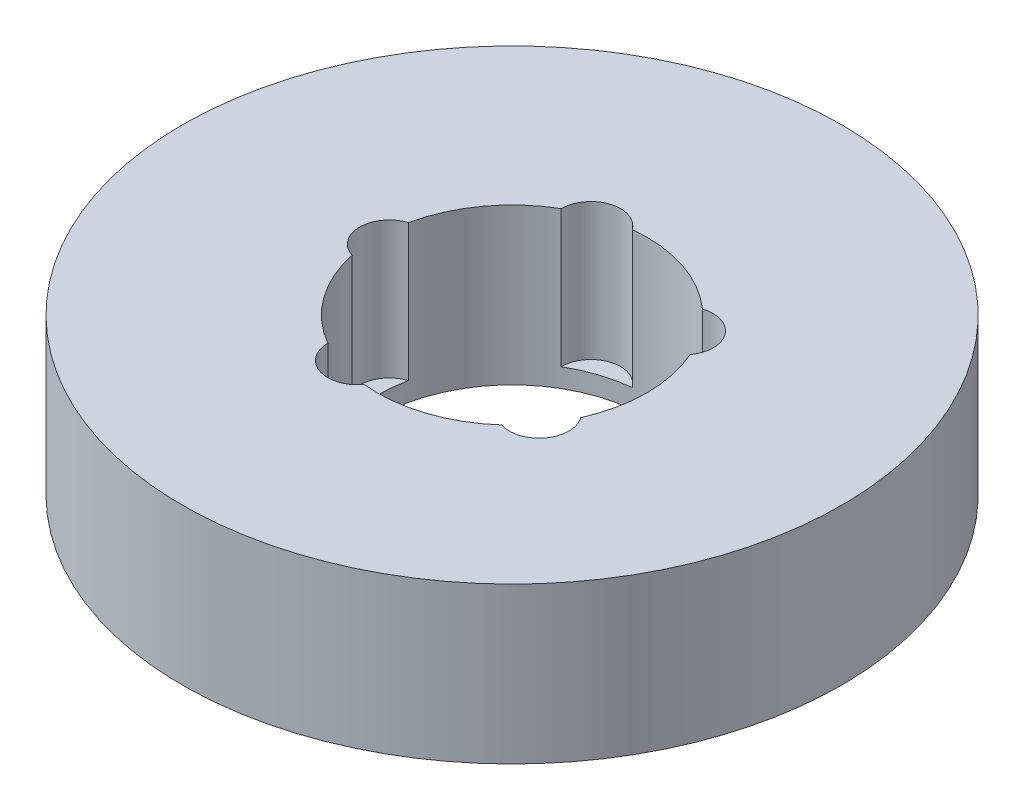
SolidWorks part; units mm, degrees
ref_plane "Front Plane" through (0, 0, 0) normal (0, 0, 1) x (1, 0, 0)
ref_plane "Top Plane" through (0, 0, 0) normal (0, 1, 0) x (1, 0, 0)
ref_plane "Right Plane" through (0, 0, 0) normal (1, 0, 0) x (0, 0, -1)
sketch "Sketch1" plane through (0, 0, 0) normal (0, 1, 0) x (1, 0, 0)
  circle A0 centre (0, 0) radius 55
  dimension "FLANGE_OD" = 110
extrude "Boss-Extrude1" add sketch "Sketch1" along normal blind 26
sketch "Sketch2" plane through (0, 0, 0) normal (0, 1, 0) x (1, 0, 0)
  circle A0 centre (0, 0) radius 22.5
  dimension "BORE_D" = 45
extrude "Cut-Extrude1" cut sketch "Sketch2" along normal through all
sketch "Sketch3" plane through (0, 26, 0) normal (0, 1, 0) x (1, 0, 0)
  circle A0 centre (0, 0) radius 20.486 construction
  circle A1 centre (-20.486, 0) radius 4.9498
  dimension "BOLT_D" = 9.8995
  dimension "BOLT_PCD" = 40.972
extrude "Cut-Extrude2" cut sketch "Sketch3" against normal blind 22.836
pattern_circular "CirPattern1" count 5 over 360 about axis through (0, 0, 0) along (0, 1, 0) of "Cut-Extrude2"
